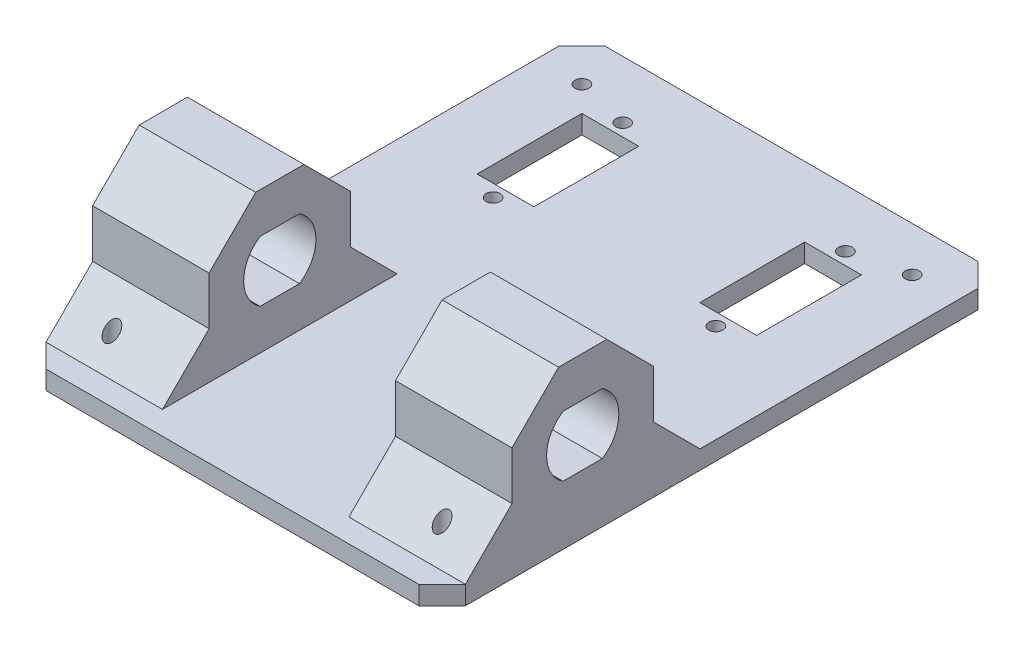
SolidWorks part; units mm, degrees
ref_plane "Front Plane" through (0, 0, 0) normal (0, 0, 1) x (1, 0, 0)
ref_plane "Top Plane" through (0, 0, 0) normal (0, 1, 0) x (1, 0, 0)
ref_plane "Right Plane" through (0, 0, 0) normal (1, 0, 0) x (0, 0, -1)
sketch "Sketch1" plane through (0, 0, 0) normal (0, 1, 0) x (1, 0, 0)
  line L5 (-45, 60) -> (45, 60)
  line L6 (-45, 60) -> (-45, -60)
  line L7 (-45, -60) -> (45, -60)
  line L12 (45, 60) -> (45, -60)
  line L13 (-45, 60) -> (45, -60) construction
  line L31 (-45, -60) -> (45, 60) construction
  point P0 (0, 0)
  dimension "D1" = 90
  dimension "D2" = 120
extrude "Boss-Extrude2" add sketch "Sketch1" along normal blind 4 contours L6 L5 L12 L7
sketch "Sketch5" plane through (0, 4, 0) normal (0, 1, 0) x (1, 0, 0)
  line L0 (-45, 60) -> (45, 60) construction
  line L1 (-30, 45) -> (-17.8, 45)
  line L2 (-30, 45) -> (-30, 22.5)
  line L3 (-30, 22.5) -> (-17.8, 22.5)
  line L4 (-17.8, 45) -> (-17.8, 22.5)
  line L5 (-30, 45) -> (-17.8, 22.5) construction
  line L6 (-30, 22.5) -> (-17.8, 45) construction
  line L7 (-45, 60) -> (-45, -60) construction
  line L8 (0, -55) -> (0, 55) construction
  line L9 (30, 22.5) -> (17.8, 45) construction
  line L10 (30, 45) -> (17.8, 22.5) construction
  line L11 (17.8, 45) -> (17.8, 22.5)
  line L12 (30, 22.5) -> (17.8, 22.5)
  line L13 (30, 45) -> (30, 22.5)
  line L14 (30, 45) -> (17.8, 45)
  point P0 (-23.9, 33.75)
  point P15 (23.9, 33.75)
  dimension "D1" = 15
  dimension "D2" = 15
  dimension "D3" = 12.2
  dimension "D4" = 22.5
extrude "Cut-Extrude1" cut sketch "Sketch5" against normal through all
sketch "Sketch10" plane through (0, 0, 0) normal (1, 0, 0) x (0, 0, -1)
  line L0 (60, 4) -> (-60, 4) construction
  line L1 (-45, 4) -> (-14.65, 4)
  line L2 (-45, 4) -> (-45, 34.35)
  line L3 (-45, 34.35) -> (-14.65, 34.35)
  line L4 (-14.65, 4) -> (-14.65, 34.35)
  line L5 (-34.0455, 25.675) -> (-25.6045, 25.675)
  line L6 (-60, 4) -> (-60, 0) construction
  line L7 (-45, 34.35) -> (-14.65, 4) construction
  line L8 (-45, 4) -> (-14.65, 34.35) construction
  line L9 (-39.1014, 19.175) -> (-19.2295, 19.175) construction
  line L10 (-34.0455, 12.675) -> (-25.6045, 12.675)
  circle A0 centre (-29.825, 19.175) radius 7.75
  dimension "D3" = 15.5
  dimension "D1" = 30.35
  dimension "D2" = 15
  dimension "D5" = 13
extrude "Boss-Extrude4" add sketch "Sketch10" against normal blind 25 from surface contours L1 L4 L3 L2 A0 | L5 A0 | L10 A0 region at (0, 19.175, 44.5708) region at (0, 26.1786, 29.825) region at (0, 12.1714, 29.825) starting at face at (45, 2, 0)
extrude "Boss-Extrude5" add sketch "Sketch10<4>" along normal blind 25 from surface contours L1 L4 L3 L2 A0 | L5 A0 | L10 A0 region at (0, 19.175, 44.5708) region at (0, 26.1786, 29.825) region at (0, 12.1714, 29.825) starting at face at (-45, 2, 0)
sketch "Sketch10<4>" plane through (0, 0, 0) normal (1, 0, 0) x (0, 0, -1) same geometry as "Sketch10"
chamfer "Chamfer6" distance 5 angle 45 4 edges at (45, 2, -60) (-45, 2, -60) (-45, 2, 60) (45, 2, 60)
chamfer "Chamfer7" distance 10 angle 45 8 edges at (32.5, 4, 45) (32.5, 4, 14.65) (32.5, 34.35, 14.65) (32.5, 34.35, 45) (-32.5, 34.35, 45) (-32.5, 34.35, 14.65) (-32.5, 4, 14.65) (-32.5, 4, 45)
sketch "Sketch13" plane through (0, 0, 0) normal (0, -1, 0) x (1, 0, 0)
  line L4 (-42.5, 57.5) -> (-16.868, 31.868) construction
  line L6 (-40, 60) -> (-45, 55) construction
  point P7 (-35.4289, 50.4289)
  point P14 (-42.5, 57.5)
  dimension "D1" = 10
hole_wizard "Ø3.0 (3) Diameter Hole2" positions "Sketch13" profile "Sketch14" hole size "Ø3.0" standard "ANSI Metric" end condition through all
sketch "Sketch14" plane through (-35.4289, 0, 50.4289) normal (1, 0, 0) x (0, 0, -1)
  line L0 (0, 0) -> (0, 34.35)
  line L1 (0, 34.35) -> (1.5, 34.35)
  line L2 (1.5, 34.35) -> (1.5, 0)
  line L5 (1.5, 0) -> (0, 0)
  line L11 (0, -6.35) -> (0, 107.95) construction
  dimension "Thru Hole Dia." = 3
  dimension "Thru Hole Depth" = 34.35
mirror "Mirror9" about plane through (0, 0, 0) normal (0, 0, 1) of "Ø3.0 (3) Diameter Hole2" second plane through (0, 0, 0) second plane normal (1, 0, 0)
sketch "Sketch15" plane through (0, 0, 0) normal (0, -1, 0) x (1, 0, 0)
  line L0 (-30, -33.75) -> (-17.8, -33.75) construction
  line L1 (-30, -45) -> (-30, -22.5) construction
  line L2 (-17.8, -22.5) -> (-17.8, -45) construction
  point P0 (-23.9, -19.85)
  point P1 (-23.9, -47.65)
  point P3 (-23.9, -33.75)
  dimension "D1" = 13.9
  dimension "D2" = 13.9
hole_wizard "Ø3.0 (3) Diameter Hole3" positions "Sketch15" profile "Sketch16" hole size "Ø3.0" standard "ANSI Metric" end condition through all
sketch "Sketch16" plane through (-23.9, 0, -19.85) normal (1, 0, 0) x (0, 0, -1)
  line L0 (0, 0) -> (0, 34.35)
  line L1 (0, 34.35) -> (1.5, 34.35)
  line L2 (1.5, 34.35) -> (1.5, 0)
  line L5 (1.5, 0) -> (0, 0)
  line L11 (0, -6.35) -> (0, 107.95) construction
  dimension "Thru Hole Dia." = 3
  dimension "Thru Hole Depth" = 34.35
mirror "Mirror10" about plane through (0, 0, 0) normal (1, 0, 0) of "Ø3.0 (3) Diameter Hole3"
